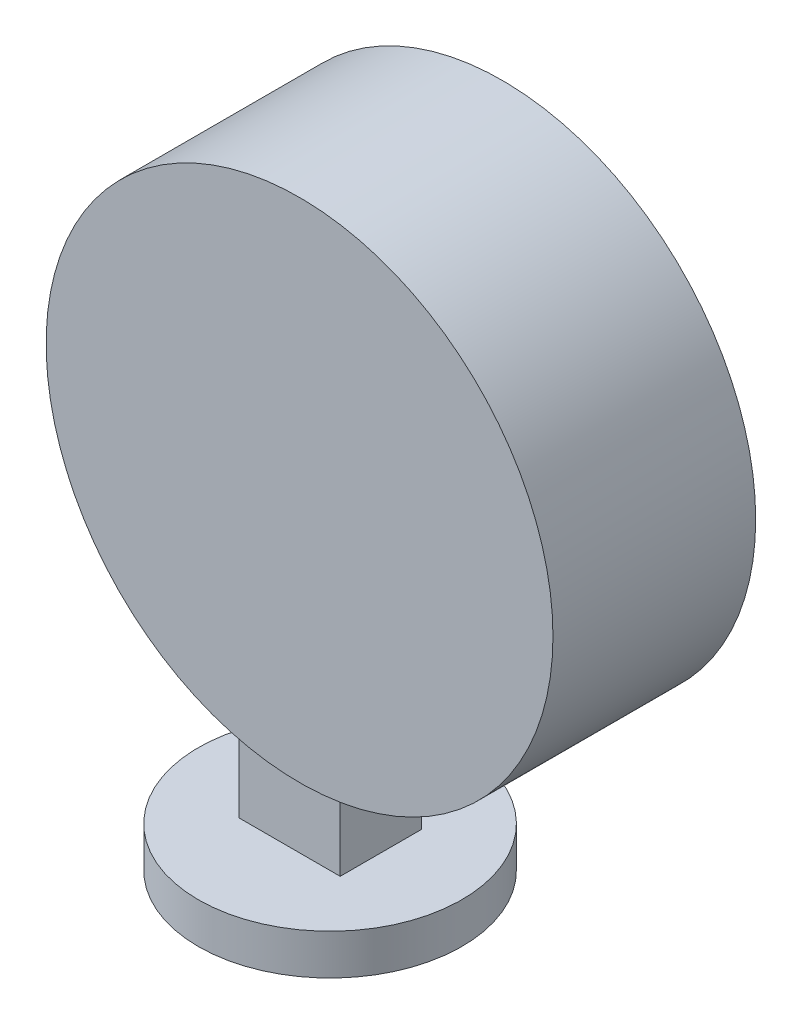
SolidWorks part; units mm, degrees
ref_plane "Front Plane" through (0, 0, 0) normal (0, 0, 1) x (1, 0, 0)
ref_plane "Top Plane" through (0, 0, 0) normal (0, 1, 0) x (1, 0, 0)
ref_plane "Right Plane" through (0, 0, 0) normal (1, 0, 0) x (0, 0, -1)
sketch "Sketch1" plane through (0, 0, 0) normal (0, 1, 0) x (1, 0, 0)
  circle A0 centre (0, 0) radius 6.5
  dimension "D1" = 13
extrude "Boss-Extrude1" add sketch "Sketch1" along normal blind 2
sketch "Sketch2" plane through (0, 0, 0) normal (0, 0, 1) x (1, 0, 0)
  line L0 (6.5, 2) -> (-6.5, 2) construction
  line L1 (6.5, 2) -> (-6.5, 2) construction
  line L2 (-2.5, 2) -> (-2.5, 17.0058)
  line L3 (2.5, 2) -> (2.5, 17.0058)
  line L4 (-2.5, 2) -> (2.5, 2)
  arc A0 (-2.5, 17.0058) -> (3.4942, 23) centre (3.4942, 17.0058) cw
  arc A1 (2.5, 17.0058) -> (3.4942, 18) centre (3.4942, 17.0058) cw
  arc A2 (3.4942, 18) -> (3.4942, 23) centre (3.4942, 20.5) ccw
  point P10 (0, 2)
  dimension "D1" = 5
  dimension "D2" = 90
  dimension "D3" = 90
  dimension "D4" = 5
  dimension "D5" = 21
extrude "Boss-Extrude2" add sketch "Sketch2" along normal blind 2 and the other way blind 2
sketch "Sketch3" plane through (0, 0, 0) normal (0, 0, 1) x (1, 0, 0)
  arc A0 (3.4942, 18) -> (3.4942, 23) centre (3.4942, 20.5) ccw construction
  arc A1 (3.4942, 18) -> (3.4942, 23) centre (3.4942, 20.5) ccw construction
  circle A2 centre (3.4942, 20.5) radius 12.5
  dimension "D1" = 25
extrude "Boss-Extrude3" add sketch "Sketch3" along normal blind 5 and the other way blind 5
